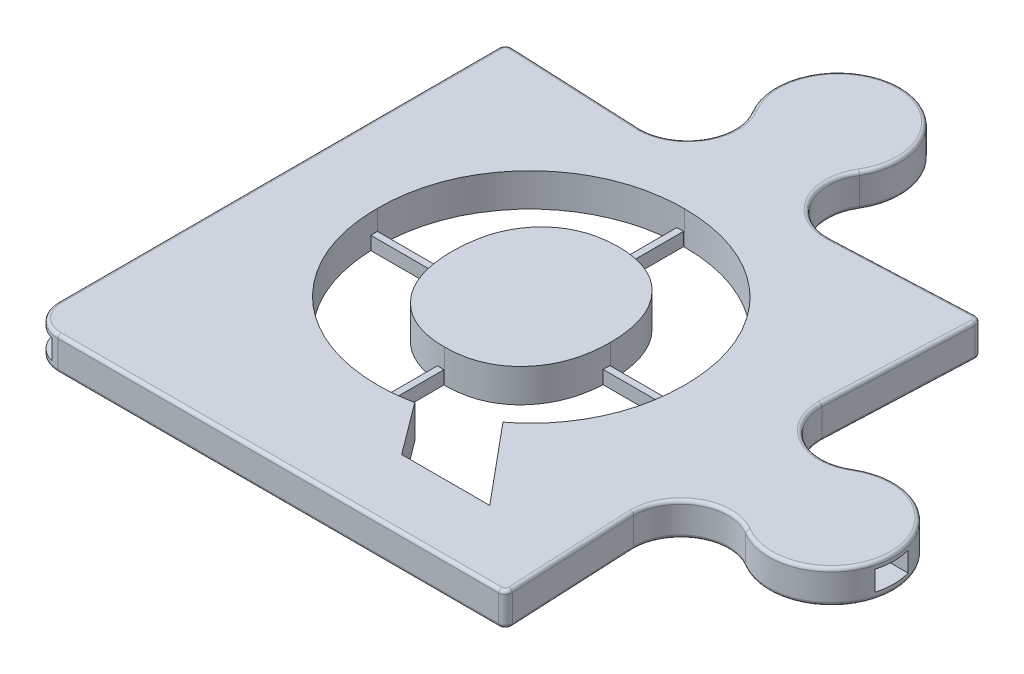
SolidWorks part; units mm, degrees
ref_plane "Front Plane" through (0, 0, 0) normal (0, 0, 1) x (1, 0, 0)
ref_plane "Top Plane" through (0, 0, 0) normal (0, 1, 0) x (1, 0, 0)
ref_plane "Right Plane" through (0, 0, 0) normal (1, 0, 0) x (0, 0, -1)
sketch "Sketch1" plane through (0, 0, 0) normal (0, 1, 0) x (1, 0, 0)
  line L0 (-31, -36) -> (37, -36) construction
  line L1 (-36, 37) -> (-36, -31) construction
  line L2 (-14.1421, 36) -> (-36, 37) construction
  line L3 (37, 37) -> (14.1421, 36) construction
  line L4 (36, 13.1421) -> (37, 37) construction
  line L5 (37, -36) -> (36, -15.1421) construction
  line L6 (-35.4, 36.3719) -> (-35.4, -31)
  line L7 (-36, 36) -> (36, 36) construction
  line L8 (-36, 36) -> (-36, -36) construction
  line L9 (-36, -36) -> (36, -36) construction
  line L10 (36, 36) -> (36, -36) construction
  line L11 (-31, -35.4) -> (36.3705, -35.4)
  line L12 (36.3705, -35.4) -> (35.4, -15.1568)
  line L13 (35.4, 13.155) -> (36.3732, 36.372)
  line L14 (36.3732, 36.372) -> (14.1555, 35.4)
  line L15 (-14.1562, 35.4) -> (-35.4, 36.3719)
  line L16 (-30, -24) -> (30, -24) construction
  line L17 (-30, 29) -> (30, 29) construction
  line L18 (-30, 29) -> (-30, -31) construction
  line L19 (-30, -31) -> (30, -31) construction
  line L20 (30, 29) -> (30, -31) construction
  line L21 (-30, 24) -> (30, 24) construction
  line L22 (-30, 24) -> (-30, -26) construction
  line L23 (-30, -26) -> (30, -26) construction
  line L24 (30, 24) -> (30, -26) construction
  arc A0 (-36, -31) -> (-31, -36) centre (-31, -31) ccw construction
  arc A1 (-14.1421, 36) -> (-8.571, 45.8485) centre (-14.1421, 42.5) ccw construction
  arc A2 (8.571, 45.8485) -> (-8.571, 45.8485) centre (0, 51) ccw construction
  arc A3 (8.571, 45.8485) -> (14.1421, 36) centre (14.1421, 42.5) ccw construction
  arc A4 (36, 13.1421) -> (45.8485, 7.571) centre (42.5, 13.1421) ccw construction
  arc A5 (45.8485, -9.571) -> (45.8485, 7.571) centre (51, -1) ccw construction
  arc A6 (45.8485, -9.571) -> (36, -15.1421) centre (42.5, -15.1421) ccw construction
  arc A7 (-35.4, -31) -> (-31, -35.4) centre (-31, -31) ccw
  arc A8 (46.1576, -9.0567) -> (35.4, -15.1568) centre (42.5, -15.1421) ccw
  arc A9 (46.1576, -9.0567) -> (46.1576, 7.0567) centre (51, -1) ccw
  arc A10 (35.4, 13.155) -> (46.1576, 7.0567) centre (42.5, 13.1421) ccw
  arc A11 (8.0567, 46.1576) -> (14.1555, 35.4) centre (14.1421, 42.5) ccw
  arc A12 (8.0567, 46.1576) -> (-8.0567, 46.1576) centre (0, 51) ccw
  arc A13 (-14.1562, 35.4) -> (-8.0567, 46.1576) centre (-14.1421, 42.5) ccw
  point P32 (36, 0)
  point P34 (0, 36)
  dimension "D5" = 6.5
  dimension "D6" = 10
  dimension "D7" = 6.5
  dimension "D13" = 5
  dimension "D9" = 10
  dimension "D11" = 6.5
  dimension "D12" = 6.5
  dimension "D1" = 72
  dimension "D2" = 1
  dimension "D3" = 1
  dimension "D4" = 15
  dimension "D8" = 1
  dimension "D10" = 35
  dimension "D14" = 15
  dimension "D15" = 36
  dimension "D16" = 1
  dimension "D18" = 60
  dimension "D19" = 60
  dimension "D20" = 5
  dimension "D21" = 6
  dimension "D22" = 5
  dimension "D23" = 50
  dimension "D24" = 2
  dimension "D17" = 0.6
extrude "Boss-Extrude1" add sketch "Sketch1" along normal blind 5
sketch "Sketch6" plane through (0, 0, 0) normal (0, -1, 0) x (1, 0, 0)
  line L0 (-35.4, -36.3719) -> (-35.4, 31) construction
  line L1 (-35.4, 17.9) -> (-27.4, 17.9)
  line L2 (-35.4, 17.9) -> (-35.4, -16.1)
  line L3 (-35.4, -16.1) -> (-27.4, -16.1)
  line L4 (-27.4, 17.9) -> (-27.4, -16.1)
  line L5 (-31, 35.4) -> (36.3705, 35.4) construction
  line L6 (-35.4, 14.65) -> (-30.4, 14.65)
  line L7 (-35.4, 14.65) -> (-35.4, -12.85)
  line L8 (-35.4, -12.85) -> (-30.4, -12.85)
  line L9 (-30.4, 14.65) -> (-30.4, -12.85)
  point P15 (-27.4, 0.9)
  point P16 (-30.4, 0.9)
  line M28 (-35.4, 31) -> (-35.4, -36.3719)
  dimension "D1" = 8
  dimension "D2" = 20.75
  dimension "D3" = 27.5
  dimension "D4" = 5
  dimension "D5" = 34
extrude "Cut-Extrude3" cut sketch "Sketch6" against normal blind 3 from offset 1 contours L6 L9 L8 L3 L4 L1 M28 | L9 L6 L2 L8 region at (-29.8665, 0, 0.9) region at (-32.9, 0, 0.9) offset against normal yes
extrude "Cut-Extrude4" cut sketch "Sketch6<3>" against normal up to next contours L9 L6 L2 L8 region at (-32.9, 0, 0.9)
sketch "Sketch6<3>" plane through (0, 0, 0) normal (0, -1, 0) x (1, 0, 0) same geometry as "Sketch6"
sketch "Sketch8" plane through (0, 0, 0) normal (0, -1, 0) x (1, 0, 0)
  line L1 (-2.5, -51.4) -> (2.5, -51.4)
  line L2 (-2.5, -51.4) -> (-2.5, -60.4)
  line L3 (-2.5, -60.4) -> (2.5, -60.4)
  line L4 (2.5, -51.4) -> (2.5, -60.4)
  line L5 (51.4, 3.5) -> (60.4, 3.5)
  line L6 (51.4, 3.5) -> (51.4, -1.5)
  line L7 (51.4, -1.5) -> (60.4, -1.5)
  line L8 (60.4, 3.5) -> (60.4, -1.5)
  arc A0 (-8.0567, -46.1576) -> (8.0567, -46.1576) centre (0, -51) ccw construction
  arc A1 (46.1576, -7.0567) -> (46.1576, 9.0567) centre (51, 1) ccw construction
  point P4 (0, -60.4)
  point P13 (60.4, 1)
  dimension "D1" = 5
  dimension "D2" = 9
  dimension "D3" = 5
  dimension "D4" = 9
extrude "Cut-Extrude5" cut sketch "Sketch8" against normal blind 3 from offset 1 offset against normal yes
sketch "Sketch9" plane through (0, 0, 0) normal (0, -1, 0) x (1, 0, 0)
  line L0 (-31, 35.4) -> (36.3705, 35.4) construction
  line L1 (-35.4, 14.65) -> (-35.4, 31) construction
  line L2 (-31.7636, 35.3332) -> (-35.4, 31) construction
  line L3 (-33.2571, 29.735) -> (-30.0429, 33.565) construction
  line L4 (-30.0429, 33.565) -> (-33.2571, 29.735) construction
  line L5 (-30.0429, 33.565) -> (-32.7119, 35.8048)
  line L6 (-33.2571, 29.735) -> (-35.926, 31.9747)
  line L7 (-32.7119, 35.8048) -> (-35.926, 31.9747)
  circle A0 centre (-31.65, 31.65) radius 2.5
  arc A1 (-31, 35.4) -> (-35.4, 31) centre (-31, 31) ccw construction
  arc M41 (-31, 35.4) -> (-35.4, 31) centre (-31, 31) ccw
  dimension "D1" = 5
  dimension "D3" = 3.75
  dimension "D4" = 5.6569
  dimension "D2" = 3.75
extrude "Cut-Extrude6" cut sketch "Sketch9" against normal blind 3 from offset 1 contours A0 L5 L6 M41 | A0 L5 region at (-33.6239, 0, 33.3064) region at (-31.65, 0, 31.65) offset against normal yes
sketch "Sketch11" plane through (-35.4, 0, 0) normal (-1, 0, 0) x (0, 0, 1)
  line L0 (-13.155, 0) -> (-36.372, 0) construction
  line L1 (-25.1, 3) -> (-19.1, 3)
  line L2 (-25.1, 3) -> (-25.1, 1.5)
  line L3 (-25.1, 1.5) -> (-19.1, 1.5)
  line L4 (-19.1, 3) -> (-19.1, 1.5)
  line L5 (-16.1, 4) -> (-16.1, 1) construction
  line L6 (35.4, 0) -> (15.1568, 0) construction
  line L7 (20.9, 3) -> (26.9, 3)
  line L8 (20.9, 3) -> (20.9, 1.5)
  line L9 (20.9, 1.5) -> (26.9, 1.5)
  line L10 (26.9, 3) -> (26.9, 1.5)
  line L12 (17.9, 4) -> (17.9, 1) construction
  dimension "D1" = 3
  dimension "D2" = 1.5
  dimension "D3" = 3
  dimension "D4" = 6
  dimension "D5" = 3
  dimension "D6" = 1.5
  dimension "D7" = 6
  dimension "D8" = 3
fillet "Fillet1" radius 0.5 17 edges at (-35.4, 0, 22.825) (-34.1113, 0, 34.1113) (2.6853, 0, 35.4) (35.8853, 0, 25.2784) (38.9978, 0, 8.966) (60.4, 0, 1) (38.9986, 0, -6.9655) (35.8866, 0, -24.7635) (25.2643, 0, -35.886) (7.9657, 0, -38.9984) (0, 0, -60.4) (-7.9658, 0, -38.9981) (-24.7781, 0, -35.886) (-35.4, 0, -24.611) (-32.9, 0, -12.85) (-30.4, 0, 0.9) (-32.9, 0, 14.65)
fillet "Fillet2" radius 0.5 13 edges at (-7.9658, 5, -38.9981) (0, 5, -60.4) (7.9657, 5, -38.9984) (25.2643, 5, -35.886) (35.8866, 5, -24.7635) (38.9986, 5, -6.9655) (60.4, 5, 1) (38.9978, 5, 8.966) (35.8853, 5, 25.2784) (2.6853, 5, 35.4) (-34.1113, 5, 34.1113) (-35.4, 5, -2.686) (-24.7781, 5, -35.886)
fillet "Fillet3" radius 1 9 edges at (36.2202, 0.1464, -36.2187) (36.2202, 4.8536, -36.2187) (36.3732, 2.5, -36.372) (-35.2536, 0.1464, -36.2186) (-35.2536, 4.8536, -36.2186) (36.2169, 0.1464, 35.2536) (36.2169, 4.8536, 35.2536) (36.3705, 2.5, 35.4) (-35.4, 2.5, -36.3719)
extrude "Cut-Extrude9" cut sketch "Sketch11" against normal blind 3
chamfer "Chamfer1" distance 1 angle 50 2 edges at (-35.4, 1.5, 23.9) (-35.4, 1.5, -22.1) first distance on face at (-35.4, 2.25, -22.1)
sketch "Sketch12" plane through (0, 5, 0) normal (0, 1, 0) x (1, 0, 0)
  text T0 "Q" font "Poppins" height 45
  point P1 (-9.1109, -2.014)
extrude "Cut-Extrude10" cut sketch "Sketch12" against normal through all
sketch "Sketch13" plane through (0, 0, 0) normal (0, -1, 0) x (1, 0, 0)
  line L0 (10.4808, 25.1626) -> (4.7027, 17.4091) construction
  line L1 (-1.4, 20.3408) -> (-0.4, 20.3408)
  line L2 (-1.4, 20.3408) -> (-1.4, -30.626)
  line L3 (-1.4, -30.626) -> (-0.4, -30.626)
  line L4 (-0.4, 20.3408) -> (-0.4, -30.626)
  line L5 (-25.0897, -4.1) -> (24.4056, -4.1)
  line L6 (-25.0897, -4.1) -> (-25.0897, -5.1)
  line L7 (-25.0897, -5.1) -> (24.4056, -5.1)
  line L8 (24.4056, -4.1) -> (24.4056, -5.1)
  line L9 (9.7356, 24.1626) -> (23.7433, 24.1626)
  line L10 (9.7356, 24.1626) -> (9.7356, 25.1626)
  line L11 (9.7356, 25.1626) -> (23.7433, 25.1626)
  line L12 (23.7433, 24.1626) -> (23.7433, 25.1626)
  line L13 (35.3215, 34.9) -> (-31, 34.9) construction
  line L14 (-35.4, 17.9) -> (-35.4, -16.1) construction
  line L15 (-31, 35.4) -> (35.3215, 35.4) construction
  line M29 (10.4808, 25.1626) -> (23.7433, 25.1626)
  line M30 (23.7433, 25.1626) -> (13.8752, 13.3098)
  line M36 (4.7027, 17.4091) -> (10.4808, 25.1626)
  dimension "D1" = 1
  dimension "D2" = 1
  dimension "D3" = 1
  dimension "D4" = 40
  dimension "D5" = 34
  dimension "D6" = 49.4953
  dimension "D7" = 10.3103
  dimension "D8" = 50.9668
  dimension "D9" = 15.0592
extrude "Boss-Extrude2" add sketch "Sketch13" against normal blind 2 contours L9 M36 M30 M29 | L5 L8 L7 L6 | L2 L3 L4 L1 region at (16.718, 0, 24.6632)
